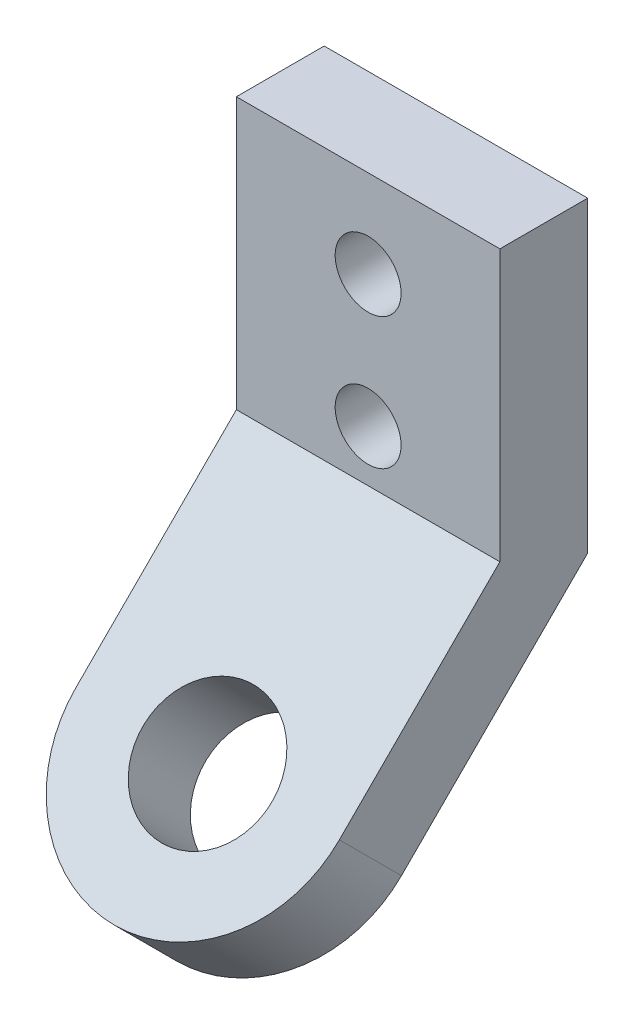
SolidWorks part; units mm, degrees
ref_plane "Front Plane" through (0, 0, 0) normal (1, 0, 0) x (0, 1, 0)
ref_plane "Top Plane" through (0, 0, 0) normal (0, 0, 1) x (0, 1, 0)
ref_plane "Right Plane" through (0, 0, 0) normal (0, 1, 0) x (-1, 0, 0)
sketch "Sketch2" plane through (0, 0, 0) normal (1, 0, 0) x (0, 1, 0)
  line L0 (0, 0) -> (177.8, 0)
  line L1 (177.8, 0) -> (177.8, 50.8)
  line L2 (177.8, 50.8) -> (21.042, 50.8)
  line L3 (21.042, 50.8) -> (-125.6953, 197.5374)
  line L4 (-125.6953, 197.5374) -> (-161.6164, 161.6164)
  line L5 (-161.6164, 161.6164) -> (0, 0)
  dimension "D1" = 50.8
  dimension "D2" = 177.8
  dimension "D3" = 45
  dimension "D4" = 207.518
  dimension "D5" = 50.8
extrude "Boss-Extrude1" add sketch "Sketch2" along normal blind 76.2 contours L5 L0 L1 L2 L3 L4
sketch "Sketch3" plane through (0, 35.921, 35.921) normal (0, 0.7071, 0.7071) x (-1, 0, 0)
  line L0 (0, 21.042) -> (0, 228.56) construction
  line L1 (-76.2, 228.56) -> (0, 228.56) construction
  line L2 (-76.2, 21.042) -> (-76.2, 228.56) construction
  line L3 (-76.2, 21.042) -> (-76.2, 228.56)
  line L4 (-76.2, 228.56) -> (0, 228.56)
  circle A0 centre (0, 152.36) radius 37.465
  circle A1 centre (0, 152.36) radius 76.2
  point P10 (0, 0)
  line M3 (0, 21.042) -> (0, 228.56)
  line M4 (0, 228.56) -> (-76.2, 228.56)
  line M5 (-76.2, 228.56) -> (-76.2, 21.042)
  dimension "D1" = 74.93
extrude "Cut-Extrude1" cut sketch "Sketch3" against normal through all contours A1 M4 M5 | A0 M3 region at (59.1794, -113.6599, 185.502) region at (15.9006, -71.8138, 143.6558)
sketch "Sketch4" plane through (0, 0, 50.8) normal (0, 0, 1) x (1, 0, 0)
  line L0 (0, 177.8) -> (0, 21.042) construction
  line L1 (76.2, 177.8) -> (0, 177.8) construction
  circle A0 centre (0, 127) radius 19.05
  circle A1 centre (0, 50.8) radius 19.05
  dimension "D1" = 38.1
  dimension "D2" = 50.8
  dimension "D3" = 76.2
extrude "Cut-Extrude2" cut sketch "Sketch4" against normal through all
mirror "Mirror1" about plane through (0, 0, 0) normal (1, 0, 0) of bodies 103
